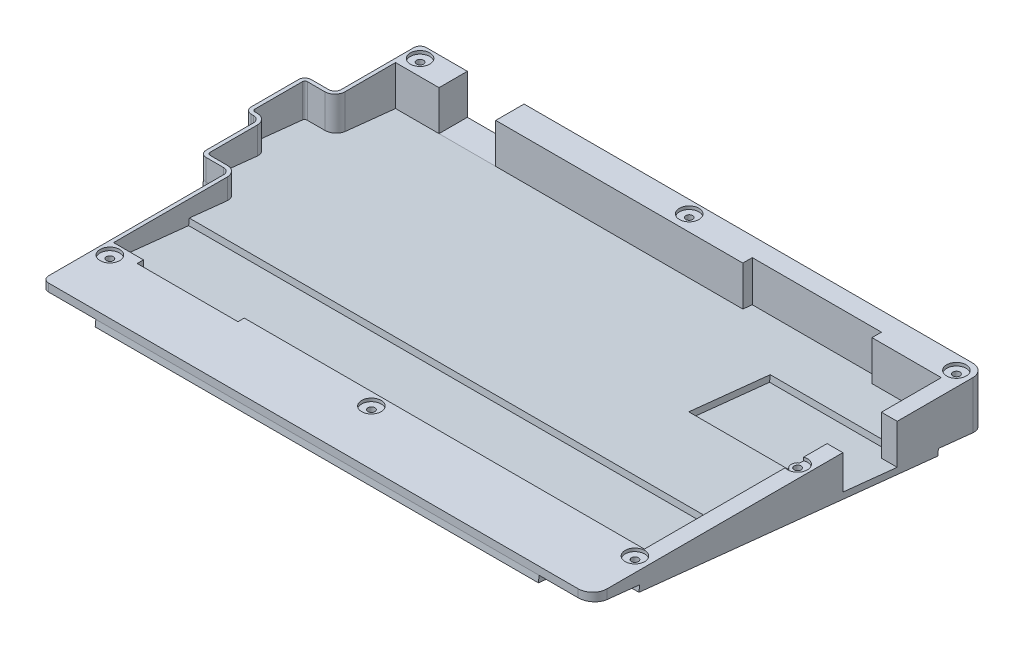
SolidWorks part; units mm, degrees
ref_plane "Front Plane" through (0, 0, 0) normal (0, 0, 1) x (1, 0, 0)
ref_plane "Top Plane" through (0, 0, 0) normal (0, 1, 0) x (1, 0, 0)
ref_plane "Right Plane" through (0, 0, 0) normal (1, 0, 0) x (0, 0, -1)
sketch "Sketch1" plane through (0, 0, 0) normal (0, 1, 0) x (1, 0, 0)
  line L0 (138.4196, 31.7518) -> (125.4196, 31.7518)
  line L1 (-35.0204, 31.7518) -> (107.4196, 31.7518)
  line L2 (140.4196, 29.7518) -> (140.4196, 6.7018)
  line L3 (-34.0204, 3.7518) -> (-34.0204, 22.7518)
  line L4 (136.4596, 27.7518) -> (136.4396, 27.7518)
  line L5 (142.4196, 4.7018) -> (147.9496, 4.7018)
  line L6 (-34.0204, 22.7518) -> (-12.0204, 22.7518)
  line L8 (149.9496, 2.7018) -> (149.9496, -12.3482)
  line L11 (147.9496, -14.3482) -> (147.1896, -14.3482)
  line L14 (145.1896, -16.3482) -> (145.1896, -31.3982)
  line L17 (143.1896, -33.3982) -> (137.6696, -33.3982)
  line L20 (135.6696, -35.3982) -> (135.6696, -77.4982)
  line L21 (-34.0204, -25.6003) -> (-34.0204, -71.4982)
  line L23 (133.6696, -79.4982) -> (-35.0204, -79.4982)
  line L28 (-39.0204, 27.7518) -> (-39.0204, 3.7518)
  line L31 (-34.0204, 3.7518) -> (-39.0204, 3.7518)
  line L32 (-34.0204, -13.4982) -> (-39.0204, -13.4982)
  line L33 (-39.0204, -75.4982) -> (-39.0204, -13.4982)
  line L34 (-34.0204, -71.4982) -> (92.9796, -71.4982)
  line L35 (92.9796, -71.4982) -> (92.9796, -73.4982)
  line L36 (92.9796, -73.4982) -> (124.9796, -73.4982)
  line L37 (124.9796, -73.4982) -> (124.9796, -71.4982)
  line L39 (134.4706, -35.3982) -> (134.4706, -71.4982)
  line L40 (134.4706, -71.4982) -> (124.9796, -71.4982)
  line L41 (137.6696, -32.1992) -> (143.1896, -32.1992)
  line L42 (-34.0204, -13.4982) -> (-34.0204, -22.1362)
  line L43 (143.9906, -31.3982) -> (143.9906, -16.3482)
  line L44 (-12.0204, 22.7518) -> (-12.0204, 25.7518)
  line L45 (147.1896, -13.1492) -> (147.9496, -13.1492)
  line L46 (148.7506, -12.3482) -> (148.7506, 2.7018)
  line L47 (-12.0204, 25.7518) -> (28.9796, 25.7518)
  line L48 (28.9796, 25.7518) -> (28.9796, 22.7518)
  line L49 (28.9796, 22.7518) -> (107.4196, 22.7518)
  line L50 (147.9496, 3.5027) -> (142.4196, 3.5027)
  line L51 (107.4196, 22.7518) -> (107.4196, 31.7518)
  line L52 (139.2206, 6.7018) -> (139.2206, 22.7518)
  line L53 (125.4196, 31.7518) -> (125.4196, 22.7518)
  line L54 (139.2206, 22.7518) -> (125.4196, 22.7518)
  arc A0 (138.4196, 31.7518) -> (140.4196, 29.7518) centre (138.4196, 29.7518) cw
  arc A1 (140.4196, 6.7018) -> (142.4196, 4.7018) centre (142.4196, 6.7018) ccw
  arc A2 (149.9496, 2.7018) -> (147.9496, 4.7018) centre (147.9496, 2.7018) ccw
  arc A3 (149.9496, -12.3482) -> (147.9496, -14.3482) centre (147.9496, -12.3482) cw
  arc A4 (147.1896, -14.3482) -> (145.1896, -16.3482) centre (147.1896, -16.3482) ccw
  arc A5 (145.1896, -31.3982) -> (143.1896, -33.3982) centre (143.1896, -31.3982) cw
  arc A6 (-35.0204, 31.7518) -> (-39.0204, 27.7518) centre (-35.0204, 27.7518) ccw
  arc A7 (-39.0204, -75.4982) -> (-35.0204, -79.4982) centre (-35.0204, -75.4982) ccw
  arc A8 (133.6696, -79.4982) -> (135.6696, -77.4982) centre (133.6696, -77.4982) ccw
  arc A9 (135.6696, -35.3982) -> (137.6696, -33.3982) centre (137.6696, -35.3982) cw
  circle A10 centre (-34.4204, 27.1518) radius 1.1
  circle A11 centre (51.0096, 27.7518) radius 1.1
  circle A12 centre (136.4396, 27.7518) radius 1.1
  circle A13 centre (-34.4204, -74.8982) radius 1.1
  circle A14 centre (48.6296, -75.4982) radius 1.1
  circle A15 centre (131.6496, -75.4982) radius 1.1
  circle A16 centre (-35.0204, -23.8682) radius 1.1
  arc A27 (-34.0204, -22.1362) -> (-34.0204, -25.6003) centre (-35.0204, -23.8682) cw
  arc A28 (139.2206, 6.7018) -> (142.4196, 3.5027) centre (142.4196, 6.7018) ccw
  arc A29 (147.9496, 3.5027) -> (148.7506, 2.7018) centre (147.9496, 2.7018) cw
  arc A30 (148.7506, -12.3482) -> (147.9496, -13.1492) centre (147.9496, -12.3482) cw
  arc A31 (147.1896, -13.1492) -> (143.9906, -16.3482) centre (147.1896, -16.3482) ccw
  arc A32 (143.9906, -31.3982) -> (143.1896, -32.1992) centre (143.1896, -31.3982) cw
  arc A33 (137.6696, -32.1992) -> (134.4706, -35.3982) centre (137.6696, -35.3982) ccw
extrude "Boss-Extrude2" add sketch "Sketch1" against normal blind 4.7 contours L41 A33 L39 L40 L37 L36 L35 L34 L21 A27 L42 L32 L33 A7 L23 A8 L20 A9 L17 A5 L14 A4 L11 A3 L8 A2 L5 A1 L2 A0 L0 L53 L54 L52 A28 L50 A29 L46 A30 L45 A31 L43 A32 A12 A13 A14 A15 | L1 A6 L28 L31 L3 L6 L44 L47 L48 L49 L51 A11 A10 region at (138.2833, 0, -29.6154) region at (31.7683, 0, -26.4895)
move or copy body "Body-Move/Copy1" bodies to move or copy 105 104 copy no rotation origin (55.4646, -2.35, 0) rotation axis (0, 0, 1) rotation angle 180
sketch "Sketch3" plane through (149.9496, 0, 0) normal (1, 0, 0) x (0, 0, -1)
  line L0 (-79.4982, 0) -> (-79.4982, -4.7) construction
  line L1 (-79.4982, 0) -> (-79.4982, -4.7)
  line L2 (31.7518, 0) -> (31.7518, -4.7) construction
  line L3 (31.7518, 0) -> (31.7518, -4.7)
  line L5 (-79.4982, -4.7) -> (31.7518, -16.3928)
  line L6 (31.7518, -16.3928) -> (31.7518, -4.7)
  line L7 (31.7518, -4.7) -> (-79.4982, -4.7)
  line M3 (-75.4982, -4.7) -> (-13.4982, -4.7)
  dimension "D1" = 6
extrude "Boss-Extrude3" add sketch "Sketch3" against normal up to surface (188.97 mm away) contours L6 L7 L5 M3 region at (149.9496, -8.5976, 5.3315) up to face at (-39.0204, -2.35, 4.8232)
sketch "Sketch4" plane through (0, -4.7, 0) normal (0, 1, 0) x (1, 0, 0)
  line L2 (145.9496, -79.4982) -> (149.9496, -79.4982)
  line L3 (149.9496, -79.4982) -> (149.9496, -75.4982)
  line L4 (-29.4904, 6.7018) -> (-29.4904, 29.7518)
  line L5 (-27.4904, 31.7518) -> (-39.0204, 31.7518)
  line L6 (-36.2604, -14.3482) -> (-37.0204, -14.3482)
  line L7 (-39.0204, -12.3482) -> (-39.0204, -79.4982)
  line L8 (-39.0204, -79.4982) -> (-22.7404, -79.4982)
  line L9 (-24.7404, -77.4982) -> (-24.7404, -35.3982)
  line L10 (-26.7404, -33.3982) -> (-32.2604, -33.3982)
  line L11 (-34.2604, -31.3982) -> (-34.2604, -16.3482)
  line L12 (-36.2604, -14.3482) -> (-37.0204, -14.3482)
  line L13 (-39.0204, -12.3482) -> (-39.0204, -79.4982)
  line L14 (-39.0204, -79.4982) -> (-22.7404, -79.4982)
  line L15 (-24.7404, -77.4982) -> (-24.7404, -35.3982)
  line L16 (-26.7404, -33.3982) -> (-32.2604, -33.3982)
  line L17 (-34.2604, -31.3982) -> (-34.2604, -16.3482)
  line L18 (-39.0204, 31.7518) -> (-39.0204, 2.7018)
  line L19 (-37.0204, 4.7018) -> (-31.4904, 4.7018)
  line L20 (-29.4904, 6.7018) -> (-29.4904, 29.7518)
  line L21 (-27.4904, 31.7518) -> (-39.0204, 31.7518)
  line L22 (-39.0204, 31.7518) -> (-39.0204, 2.7018)
  line L23 (-37.0204, 4.7018) -> (-31.4904, 4.7018)
  line L24 (145.9496, -79.4982) -> (149.9496, -79.4982)
  line L25 (149.9496, -79.4982) -> (149.9496, -75.4982)
  line L26 (149.9496, 31.7518) -> (145.9496, 31.7518)
  line L27 (149.9496, 27.7518) -> (149.9496, 31.7518)
  line L28 (149.9496, 31.7518) -> (145.9496, 31.7518)
  line L29 (149.9496, 27.7518) -> (149.9496, 31.7518)
  arc A1 (145.9496, -79.4982) -> (149.9496, -75.4982) centre (145.9496, -75.4982) ccw
  arc A2 (145.9496, -79.4982) -> (149.9496, -75.4982) centre (145.9496, -75.4982) ccw
  arc A3 (-27.4904, 31.7518) -> (-29.4904, 29.7518) centre (-27.4904, 29.7518) ccw
  arc A4 (-37.0204, 4.7018) -> (-39.0204, 2.7018) centre (-37.0204, 2.7018) ccw
  arc A5 (-39.0204, -12.3482) -> (-37.0204, -14.3482) centre (-37.0204, -12.3482) ccw
  arc A6 (-24.7404, -77.4982) -> (-22.7404, -79.4982) centre (-22.7404, -77.4982) ccw
  arc A7 (-24.7404, -35.3982) -> (-26.7404, -33.3982) centre (-26.7404, -35.3982) ccw
  arc A8 (-34.2604, -31.3982) -> (-32.2604, -33.3982) centre (-32.2604, -31.3982) ccw
  arc A9 (-34.2604, -16.3482) -> (-36.2604, -14.3482) centre (-36.2604, -16.3482) ccw
  arc A10 (-39.0204, -12.3482) -> (-37.0204, -14.3482) centre (-37.0204, -12.3482) ccw
  arc A11 (-24.7404, -77.4982) -> (-22.7404, -79.4982) centre (-22.7404, -77.4982) ccw
  arc A12 (-24.7404, -35.3982) -> (-26.7404, -33.3982) centre (-26.7404, -35.3982) ccw
  arc A13 (-34.2604, -31.3982) -> (-32.2604, -33.3982) centre (-32.2604, -31.3982) ccw
  arc A14 (-34.2604, -16.3482) -> (-36.2604, -14.3482) centre (-36.2604, -16.3482) ccw
  arc A15 (-31.4904, 4.7018) -> (-29.4904, 6.7018) centre (-31.4904, 6.7018) ccw
  arc A16 (-27.4904, 31.7518) -> (-29.4904, 29.7518) centre (-27.4904, 29.7518) ccw
  arc A17 (-37.0204, 4.7018) -> (-39.0204, 2.7018) centre (-37.0204, 2.7018) ccw
  arc A18 (-31.4904, 4.7018) -> (-29.4904, 6.7018) centre (-31.4904, 6.7018) ccw
  arc A19 (149.9496, 27.7518) -> (145.9496, 31.7518) centre (145.9496, 27.7518) ccw
  arc A20 (149.9496, 27.7518) -> (145.9496, 31.7518) centre (145.9496, 27.7518) ccw
  dimension "D1" = 0
  dimension "D2" = 0
  dimension "D3" = 0
  dimension "D4" = 0
extrude "Cut-Extrude1" cut sketch "Sketch4" against normal through all
ref_plane "Plane4" through (0, 15, 0) normal (0, 1, 0) x (1, 0, 0)
sketch "Sketch10" plane through (0, 15, 0) normal (0, 1, 0) x (1, 0, 0)
  line L0 (-14.4904, 22.7518) -> (3.5096, 22.7518)
  line L1 (144.9496, 3.7518) -> (144.9496, -13.4982)
  line L27 (-14.4904, 31.7518) -> (-14.4904, 22.7518)
  line L28 (-14.4904, 22.7518) -> (-28.2913, 22.7518)
  line L29 (-28.2913, 22.7518) -> (-28.2913, 6.7018)
  line L30 (-31.4904, 3.5027) -> (-37.0204, 3.5027)
  line L31 (-37.8213, 2.7018) -> (-37.8213, -12.3482)
  line L32 (-37.0204, -13.1492) -> (-36.2604, -13.1492)
  line L33 (-33.0613, -16.3482) -> (-33.0613, -31.3982)
  line L34 (-32.2604, -32.1992) -> (-26.7404, -32.1992)
  line L35 (-23.5413, -35.3982) -> (-23.5413, -71.4982)
  line L36 (-23.5413, -71.4982) -> (-14.0504, -71.4982)
  line L37 (-14.0504, -71.4982) -> (-14.0504, -73.4982)
  line L38 (-14.0504, -73.4982) -> (17.9496, -73.4982)
  line L39 (17.9496, -73.4982) -> (17.9496, -71.4982)
  line L40 (17.9496, -71.4982) -> (144.9496, -71.4982)
  line L41 (144.9496, -71.4982) -> (144.9496, -25.6003)
  line L42 (144.9496, -22.1362) -> (144.9496, -13.4982)
  line L43 (144.9496, -13.4982) -> (149.9496, -13.4982)
  line L44 (149.9496, -13.4982) -> (149.9496, 3.7518)
  line L45 (149.9496, 3.7518) -> (144.9496, 3.7518)
  line L46 (144.9496, 3.7518) -> (144.9496, 22.7518)
  line L47 (144.9496, 22.7518) -> (122.9496, 22.7518)
  line L48 (122.9496, 22.7518) -> (122.9496, 25.7518)
  line L49 (122.9496, 25.7518) -> (81.9496, 25.7518)
  line L50 (81.9496, 25.7518) -> (81.9496, 22.7518)
  line L51 (81.9496, 22.7518) -> (3.5096, 22.7518)
  line L52 (3.5096, 22.7518) -> (3.5096, 31.7518)
  line L53 (3.5096, 31.7518) -> (-14.4904, 31.7518)
  line L54 (-14.4904, 31.7518) -> (-14.4904, 22.7518)
  line L55 (-14.4904, 22.7518) -> (-28.2913, 22.7518)
  line L56 (-28.2913, 22.7518) -> (-28.2913, 6.7018)
  line L57 (-31.4904, 3.5027) -> (-37.0204, 3.5027)
  line L58 (-37.8213, 2.7018) -> (-37.8213, -12.3482)
  line L59 (-37.0204, -13.1492) -> (-36.2604, -13.1492)
  line L60 (-33.0613, -16.3482) -> (-33.0613, -31.3982)
  line L61 (-32.2604, -32.1992) -> (-26.7404, -32.1992)
  line L62 (-23.5413, -35.3982) -> (-23.5413, -71.4982)
  line L63 (-23.5413, -71.4982) -> (-14.0504, -71.4982)
  line L64 (-14.0504, -71.4982) -> (-14.0504, -73.4982)
  line L65 (-14.0504, -73.4982) -> (17.9496, -73.4982)
  line L66 (17.9496, -73.4982) -> (17.9496, -71.4982)
  line L67 (17.9496, -71.4982) -> (144.9496, -71.4982)
  line L68 (144.9496, -71.4982) -> (144.9496, -25.6003)
  line L69 (144.9496, -22.1362) -> (144.9496, -13.4982)
  line L70 (144.9496, -13.4982) -> (149.9496, -13.4982)
  line L71 (149.9496, -13.4982) -> (149.9496, 3.7518)
  line L72 (149.9496, 3.7518) -> (144.9496, 3.7518)
  line L73 (144.9496, 3.7518) -> (144.9496, 22.7518)
  line L74 (144.9496, 22.7518) -> (122.9496, 22.7518)
  line L75 (122.9496, 22.7518) -> (122.9496, 25.7518)
  line L76 (122.9496, 25.7518) -> (81.9496, 25.7518)
  line L77 (81.9496, 25.7518) -> (81.9496, 22.7518)
  line L78 (81.9496, 22.7518) -> (3.5096, 22.7518)
  line L79 (3.5096, 22.7518) -> (3.5096, 31.7518)
  line L80 (3.5096, 31.7518) -> (-14.4904, 31.7518)
  arc A7 (-31.4904, 3.5027) -> (-28.2913, 6.7018) centre (-31.4904, 6.7018) ccw
  arc A8 (-37.0204, 3.5027) -> (-37.8213, 2.7018) centre (-37.0204, 2.7018) ccw
  arc A9 (-37.8213, -12.3482) -> (-37.0204, -13.1492) centre (-37.0204, -12.3482) ccw
  arc A10 (-33.0613, -16.3482) -> (-36.2604, -13.1492) centre (-36.2604, -16.3482) ccw
  arc A11 (-33.0613, -31.3982) -> (-32.2604, -32.1992) centre (-32.2604, -31.3982) ccw
  arc A12 (-23.5413, -35.3982) -> (-26.7404, -32.1992) centre (-26.7404, -35.3982) ccw
  arc A13 (144.9496, -22.1362) -> (144.9496, -25.6003) centre (145.9496, -23.8682) ccw
  arc A14 (-31.4904, 3.5027) -> (-28.2913, 6.7018) centre (-31.4904, 6.7018) ccw
  arc A15 (-37.0204, 3.5027) -> (-37.8213, 2.7018) centre (-37.0204, 2.7018) ccw
  arc A16 (-37.8213, -12.3482) -> (-37.0204, -13.1492) centre (-37.0204, -12.3482) ccw
  arc A17 (-33.0613, -16.3482) -> (-36.2604, -13.1492) centre (-36.2604, -16.3482) ccw
  arc A18 (-33.0613, -31.3982) -> (-32.2604, -32.1992) centre (-32.2604, -31.3982) ccw
  arc A19 (-23.5413, -35.3982) -> (-26.7404, -32.1992) centre (-26.7404, -35.3982) ccw
  arc A20 (144.9496, -22.1362) -> (144.9496, -25.6003) centre (145.9496, -23.8682) ccw
  dimension "D1" = 0
extrude "Cut-Extrude2" cut sketch "Sketch10" against normal through all contours A20 L69 L1 L73 L74 L75 L76 L77 L78 L0 L55 L56 A14 L57 A15 L58 A16 L59 A17 L60 A18 L61 A19 L62 L63 L64 L65 L66 L67 L68 region at (57.9798, 15, 23.6888)
sketch "Sketch11" plane through (144.9496, 0, 0) normal (-1, 0, 0) x (0, 0, 1)
  line L0 (-22.7518, -15.4469) -> (71.4982, -5.5408)
  line L1 (71.4982, -5.5408) -> (71.4982, -3.5408)
  line L2 (71.4982, 0) -> (71.4982, -5.5408) construction
  line L3 (71.4982, -3.5408) -> (-22.7518, -13.4469)
  line L4 (-22.7518, 0) -> (-22.7518, -15.4469) construction
  line L5 (-22.7518, -13.4469) -> (-22.7518, -15.4469)
  dimension "D1" = 2
  dimension "D2" = 2
extrude "Boss-Extrude4" add sketch "Sketch11" along normal up to surface (182.7709 mm away)
sketch "Sketch12" plane through (0, -10.9348, 1.1493) normal (0, 0.9945, -0.1045) x (1, 0, 0)
  line L0 (-29.4904, 7.8943) -> (-29.4904, 24.0327) construction
  line L1 (-29.4904, 24.0327) -> (-37.8213, 24.0327) construction
  line L2 (-37.8213, 24.0327) -> (-37.8213, 5.715) construction
  line L3 (-37.0204, 5.8833) -> (-31.4904, 5.8833) construction
  line L4 (-36.2604, -13.2716) -> (-37.0204, -13.2716) construction
  line L5 (-37.8213, -13.1033) -> (-37.8213, -70.7364) construction
  line L6 (-37.8213, -70.7364) -> (-24.7404, -70.7364) construction
  line L7 (-24.7404, -70.7364) -> (-24.7404, -34.4376) construction
  line L8 (-26.7404, -32.4266) -> (-32.2604, -32.4266) construction
  line L9 (-34.2604, -30.4155) -> (-34.2604, -15.2826) construction
  line L10 (-29.4904, 7.8943) -> (-29.4904, 24.0327)
  line L11 (-29.4904, 24.0327) -> (-37.8213, 24.0327)
  line L12 (-37.8213, 24.0327) -> (-37.8213, 5.715)
  line L13 (-37.0204, 5.8833) -> (-31.4904, 5.8833)
  line L14 (-36.2604, -13.2716) -> (-37.0204, -13.2716)
  line L15 (-37.8213, -13.1033) -> (-37.8213, -70.7364)
  line L16 (-37.8213, -70.7364) -> (-24.7404, -70.7364)
  line L17 (-24.7404, -70.7364) -> (-24.7404, -34.4376)
  line L18 (-26.7404, -32.4266) -> (-32.2604, -32.4266)
  line L19 (-34.2604, -30.4155) -> (-34.2604, -15.2826)
  line L20 (-37.8213, 24.0327) -> (-37.8213, 25.9101)
  line L21 (-29.4904, 24.0327) -> (-29.4904, 27.1127)
  line L22 (-29.4904, 27.1127) -> (-37.8213, 25.9101)
  ellipse E0 centre (-31.4904, 7.8943) end of major axis (-31.4904, 9.9053) minor radius 2 (-31.4904, 5.8833) -> (-29.4904, 7.8943) ccw construction
  ellipse E1 centre (-37.0204, 3.8723) end of major axis (-37.0204, 5.8833) minor radius 2 (-37.0204, 5.8833) -> (-37.8213, 5.715) ccw construction
  ellipse E2 centre (-37.0204, -11.2606) end of major axis (-37.0204, -9.2496) minor radius 2 (-37.8213, -13.1033) -> (-37.0204, -13.2716) ccw construction
  ellipse E3 centre (-26.7404, -34.4376) end of major axis (-26.7404, -32.4266) minor radius 2 (-24.7404, -34.4376) -> (-26.7404, -32.4266) ccw construction
  ellipse E4 centre (-32.2604, -30.4155) end of major axis (-32.2604, -28.4045) minor radius 2 (-34.2604, -30.4155) -> (-32.2604, -32.4266) ccw construction
  ellipse E5 centre (-36.2604, -15.2826) end of major axis (-36.2604, -13.2716) minor radius 2 (-34.2604, -15.2826) -> (-36.2604, -13.2716) ccw construction
  ellipse E6 centre (-31.4904, 7.8943) end of major axis (-31.4904, 9.9053) minor radius 2 (-31.4904, 5.8833) -> (-29.4904, 7.8943) ccw
  ellipse E7 centre (-37.0204, 3.8723) end of major axis (-37.0204, 5.8833) minor radius 2 (-37.0204, 5.8833) -> (-37.8213, 5.715) ccw
  ellipse E8 centre (-37.0204, -11.2606) end of major axis (-37.0204, -9.2496) minor radius 2 (-37.8213, -13.1033) -> (-37.0204, -13.2716) ccw
  ellipse E9 centre (-26.7404, -34.4376) end of major axis (-26.7404, -32.4266) minor radius 2 (-24.7404, -34.4376) -> (-26.7404, -32.4266) ccw
  ellipse E10 centre (-32.2604, -30.4155) end of major axis (-32.2604, -28.4045) minor radius 2 (-34.2604, -30.4155) -> (-32.2604, -32.4266) ccw
  ellipse E11 centre (-36.2604, -15.2826) end of major axis (-36.2604, -13.2716) minor radius 2 (-34.2604, -15.2826) -> (-36.2604, -13.2716) ccw
sketch "Sketch26" plane through (-37.8213, 0, 0) normal (-1, 0, 0) x (0, 0, 1)
  line L0 (14.1808, -9.5651) -> (-4.5344, -11.5322)
  line L1 (-4.5344, -13.5322) -> (14.1808, -11.5651)
  line L4 (-22.7518, -15.4469) -> (-4.5344, -13.5322)
  line L5 (-4.5344, -13.5322) -> (-4.5344, -11.5322)
  line L6 (-4.5344, -11.5322) -> (-22.7518, -13.4469)
  line L7 (-22.7518, -13.4469) -> (-22.7518, -15.4469)
  line L8 (-22.7518, -15.4469) -> (-4.5344, -13.5322)
  line L9 (-4.5344, -13.5322) -> (-4.5344, -11.5322)
  line L10 (-4.5344, -11.5322) -> (-22.7518, -13.4469)
  line L11 (-22.7518, -13.4469) -> (-22.7518, -15.4469)
  line L12 (14.1808, -9.5651) -> (14.1808, -11.5651)
  line L13 (14.1808, -11.5651) -> (71.4982, -5.5408)
  line L14 (71.4982, -5.5408) -> (71.4982, -3.5408)
  line L15 (71.4982, -3.5408) -> (14.1808, -9.5651)
  line L16 (14.1808, -9.5651) -> (14.1808, -11.5651)
  line L17 (14.1808, -11.5651) -> (71.4982, -5.5408)
  line L18 (71.4982, -5.5408) -> (71.4982, -3.5408)
  line L19 (71.4982, -3.5408) -> (14.1808, -9.5651)
  line M9 (14.1808, -9.5651) -> (14.1808, -11.5651)
  line M10 (14.1808, -11.5651) -> (71.4982, -5.5408)
  line M11 (71.4982, -5.5408) -> (71.4982, -3.5408)
  line M12 (71.4982, -3.5408) -> (14.1808, -9.5651)
  dimension "D1" = 0
  dimension "D2" = 0
extrude "Boss-Extrude10" add sketch "Sketch26" along normal blind 11 contours L10 L11 L8 L9 | L9 L1 L0 M9 | M12 M9 M10 M11 region at (-37.8213, -11.5487, 4.8232) region at (-37.8213, -7.553, 42.8395) region at (-37.8213, -13.4895, -13.6431)
sketch "Sketch28" plane through (0, -10.9348, 1.1493) normal (0, 0.9945, -0.1045) x (1, 0, 0)
  line L0 (-48.8213, 24.0327) -> (-52.7132, 28.3929)
  line L1 (-52.7132, 28.3929) -> (-29.4904, 30.8021)
  line L2 (-29.4904, 30.8021) -> (-29.4904, 24.0327)
  line L10 (-29.4904, 7.8943) -> (-29.4904, 24.0327)
  line L11 (-29.4904, 24.0327) -> (-48.8213, 24.0327)
  line L12 (-48.8213, 24.0327) -> (-48.8213, -70.7364)
  line L13 (-48.8213, -70.7364) -> (-24.7404, -70.7364)
  line L14 (-24.7404, -70.7364) -> (-24.7404, -34.4376)
  line L15 (-26.7404, -32.4266) -> (-32.2604, -32.4266)
  line L16 (-34.2604, -30.4155) -> (-34.2604, -15.2826)
  line L17 (-36.2604, -13.2716) -> (-37.0204, -13.2716)
  line L18 (-39.0204, -11.2606) -> (-39.0204, 3.8723)
  line L19 (-37.0204, 5.8833) -> (-31.4904, 5.8833)
  line L20 (-29.4904, 7.8943) -> (-29.4904, 24.0327)
  line L21 (-29.4904, 24.0327) -> (-48.8213, 24.0327)
  line L22 (-48.8213, 24.0327) -> (-48.8213, -70.7364)
  line L23 (-48.8213, -70.7364) -> (-24.7404, -70.7364)
  line L24 (-24.7404, -70.7364) -> (-24.7404, -34.4376)
  line L25 (-26.7404, -32.4266) -> (-32.2604, -32.4266)
  line L26 (-34.2604, -30.4155) -> (-34.2604, -15.2826)
  line L27 (-36.2604, -13.2716) -> (-37.0204, -13.2716)
  line L28 (-39.0204, -11.2606) -> (-39.0204, 3.8723)
  line L29 (-37.0204, 5.8833) -> (-31.4904, 5.8833)
  ellipse E6 centre (-31.4904, 7.8943) end of major axis (-31.4904, 9.9053) minor radius 2 (-31.4904, 5.8833) -> (-29.4904, 7.8943) ccw
  ellipse E7 centre (-26.7404, -34.4376) end of major axis (-26.7404, -32.4266) minor radius 2 (-24.7404, -34.4376) -> (-26.7404, -32.4266) ccw
  ellipse E8 centre (-32.2604, -30.4155) end of major axis (-32.2604, -28.4045) minor radius 2 (-34.2604, -30.4155) -> (-32.2604, -32.4266) ccw
  ellipse E9 centre (-36.2604, -15.2826) end of major axis (-36.2604, -13.2716) minor radius 2 (-34.2604, -15.2826) -> (-36.2604, -13.2716) ccw
  ellipse E10 centre (-37.0204, -11.2606) end of major axis (-37.0204, -9.2496) minor radius 2 (-39.0204, -11.2606) -> (-37.0204, -13.2716) ccw
  ellipse E11 centre (-37.0204, 3.8723) end of major axis (-37.0204, 5.8833) minor radius 2 (-37.0204, 5.8833) -> (-39.0204, 3.8723) ccw
  ellipse E12 centre (-31.4904, 7.8943) end of major axis (-31.4904, 9.9053) minor radius 2 (-31.4904, 5.8833) -> (-29.4904, 7.8943) ccw
  ellipse E13 centre (-26.7404, -34.4376) end of major axis (-26.7404, -32.4266) minor radius 2 (-24.7404, -34.4376) -> (-26.7404, -32.4266) ccw
  ellipse E14 centre (-32.2604, -30.4155) end of major axis (-32.2604, -28.4045) minor radius 2 (-34.2604, -30.4155) -> (-32.2604, -32.4266) ccw
  ellipse E15 centre (-36.2604, -15.2826) end of major axis (-36.2604, -13.2716) minor radius 2 (-34.2604, -15.2826) -> (-36.2604, -13.2716) ccw
  ellipse E16 centre (-37.0204, -11.2606) end of major axis (-37.0204, -9.2496) minor radius 2 (-39.0204, -11.2606) -> (-37.0204, -13.2716) ccw
  ellipse E17 centre (-37.0204, 3.8723) end of major axis (-37.0204, 5.8833) minor radius 2 (-37.0204, 5.8833) -> (-39.0204, 3.8723) ccw
  ellipse M17 centre (-31.4904, 7.8943) end of major axis (-31.4904, 9.9053) minor radius 2 (-31.4904, 5.8833) -> (-29.4904, 7.8943) ccw
  line M18 (-29.4904, 7.8943) -> (-29.4904, 24.0327)
  line M19 (-29.4904, 24.0327) -> (-48.8213, 24.0327)
  line M20 (-48.8213, 24.0327) -> (-48.8213, -70.7364)
  line M21 (-48.8213, -70.7364) -> (-24.7404, -70.7364)
  line M22 (-24.7404, -70.7364) -> (-24.7404, -34.4376)
  ellipse M23 centre (-26.7404, -34.4376) end of major axis (-26.7404, -32.4266) minor radius 2 (-24.7404, -34.4376) -> (-26.7404, -32.4266) ccw
  line M24 (-26.7404, -32.4266) -> (-32.2604, -32.4266)
  ellipse M25 centre (-32.2604, -30.4155) end of major axis (-32.2604, -28.4045) minor radius 2 (-32.2604, -32.4266) -> (-34.2604, -30.4155) cw
  line M26 (-34.2604, -30.4155) -> (-34.2604, -15.2826)
  ellipse M27 centre (-36.2604, -15.2826) end of major axis (-36.2604, -13.2716) minor radius 2 (-34.2604, -15.2826) -> (-36.2604, -13.2716) ccw
  line M28 (-36.2604, -13.2716) -> (-37.0204, -13.2716)
  ellipse M29 centre (-37.0204, -11.2606) end of major axis (-37.0204, -9.2496) minor radius 2 (-37.0204, -13.2716) -> (-39.0204, -11.2606) cw
  line M30 (-39.0204, -11.2606) -> (-39.0204, 3.8723)
  ellipse M31 centre (-37.0204, 3.8723) end of major axis (-37.0204, 5.8833) minor radius 2 (-39.0204, 3.8723) -> (-37.0204, 5.8833) cw
  line M32 (-37.0204, 5.8833) -> (-31.4904, 5.8833)
  dimension "D1" = 0
extrude "Cut-Extrude8" cut sketch "Sketch28" against normal blind 11 contours M32 M17 M18 M19 M20 M21 M22 M23 M24 M25 M26 M27 M28 M29 M30 M31 | L2 L1 L0 M19 region at (-39.4803, -13.7524, -25.6581) region at (-38.8035, -7.967, 29.3861)
sketch "Sketch30" plane through (122.9496, 0, 0) normal (-1, 0, 0) x (0, 0, 1)
  line L0 (-25.7518, -15.7622) -> (-22.7518, -15.4469)
  line L1 (-22.7518, -15.4469) -> (-22.7518, -13.4469)
  line L2 (-22.7518, -15.4469) -> (-22.7518, -13.4469) construction
  line L3 (-22.7518, -13.4469) -> (-25.7518, -13.7622)
  line L4 (-25.7518, 0) -> (-25.7518, -15.7622) construction
  line L5 (-25.7518, -13.7622) -> (-25.7518, -15.7622)
extrude "Boss-Extrude11" add sketch "Sketch30" along normal up to surface (41 mm away)
sketch "Sketch32" plane through (17.9496, 0, 0) normal (-1, 0, 0) x (0, 0, 1)
  line L0 (73.4982, -5.3306) -> (71.4982, -5.5408)
  line L1 (71.4982, -5.5408) -> (71.4982, -3.5408)
  line L2 (71.4982, -3.5408) -> (73.4982, -3.3306)
  line L3 (73.4982, 0) -> (73.4982, -5.3306) construction
  line L4 (73.4982, -3.3306) -> (73.4982, -5.3306)
  dimension "D1" = 2
extrude "Boss-Extrude14" add sketch "Sketch32" along normal up to surface (32 mm away)
sketch "Sketch35" plane through (0, 0, 0) normal (0, 1, 0) x (1, 0, 0)
  line L0 (149.9496, 3.7518) -> (149.9496, -13.4982)
  line L1 (149.9496, -13.4982) -> (144.9496, -13.4982)
  line L2 (144.9496, -13.4982) -> (144.9496, 3.7518)
  line L3 (144.9496, 3.7518) -> (149.9496, 3.7518)
ref_plane "Plane5" through (149.9496, -5.1204, 75.4982) normal (0, -1, 0) x (-1, 0, 0)
sketch "Sketch47" plane through (0, 0, 0) normal (0, 1, 0) x (1, 0, 0)
  circle A0 centre (145.3496, -74.8982) radius 3.1
  circle A1 centre (62.2996, -75.4982) radius 3.1
  circle A2 centre (-20.7204, -75.4982) radius 3.1
  circle A3 centre (-25.5104, 27.7518) radius 3.1
  circle A4 centre (59.9196, 27.7518) radius 3.1
  circle A5 centre (145.3496, 27.1518) radius 3.1
  circle A6 centre (145.9496, -23.8682) radius 3.1
extrude "Cut-Extrude17" cut sketch "Sketch47" against normal blind 1.8
sketch "Sketch48" plane through (0, 0, 0) normal (0, 1, 0) x (1, 0, 0)
  line L10 (145.9496, 31.7518) -> (3.5096, 31.7518)
  line L11 (3.5096, 31.7518) -> (3.5096, 22.7518)
  line L12 (3.5096, 22.7518) -> (81.9496, 22.7518)
  line L13 (81.9496, 22.7518) -> (81.9496, 25.7518)
  line L14 (81.9496, 25.7518) -> (122.9496, 25.7518)
  line L15 (122.9496, 25.7518) -> (122.9496, 22.7518)
  line L16 (122.9496, 22.7518) -> (144.9496, 22.7518)
  line L17 (144.9496, 22.7518) -> (144.9496, 3.7518)
  line L18 (144.9496, 3.7518) -> (149.9496, 3.7518)
  line L19 (149.9496, 3.7518) -> (149.9496, 27.7518)
  line L20 (145.9496, 31.7518) -> (3.5096, 31.7518)
  line L21 (3.5096, 31.7518) -> (3.5096, 22.7518)
  line L22 (3.5096, 22.7518) -> (81.9496, 22.7518)
  line L23 (81.9496, 22.7518) -> (81.9496, 25.7518)
  line L24 (81.9496, 25.7518) -> (122.9496, 25.7518)
  line L25 (122.9496, 25.7518) -> (122.9496, 22.7518)
  line L26 (122.9496, 22.7518) -> (144.9496, 22.7518)
  line L27 (144.9496, 22.7518) -> (144.9496, 3.7518)
  line L28 (144.9496, 3.7518) -> (149.9496, 3.7518)
  line L29 (149.9496, 3.7518) -> (149.9496, 27.7518)
  line L47 (144.9496, -13.4982) -> (144.9496, -20.9339)
  line L48 (144.9496, -26.8025) -> (144.9496, -71.4982)
  line L49 (144.9496, -71.4982) -> (17.9496, -71.4982)
  line L50 (17.9496, -71.4982) -> (17.9496, -73.4982)
  line L51 (17.9496, -73.4982) -> (-14.0504, -73.4982)
  line L52 (-14.0504, -73.4982) -> (-14.0504, -71.4982)
  line L53 (-14.0504, -71.4982) -> (-23.5413, -71.4982)
  line L54 (-23.5413, -71.4982) -> (-23.5413, -35.3982)
  line L55 (-26.7404, -32.1992) -> (-32.2604, -32.1992)
  line L56 (-33.0613, -31.3982) -> (-33.0613, -16.3482)
  line L57 (-36.2604, -13.1492) -> (-37.0204, -13.1492)
  line L58 (-37.8213, -12.3482) -> (-37.8213, 2.7018)
  line L59 (-37.0204, 3.5027) -> (-31.4904, 3.5027)
  line L60 (-28.2913, 6.7018) -> (-28.2913, 22.7518)
  line L61 (-28.2913, 22.7518) -> (-14.4904, 22.7518)
  line L62 (-14.4904, 22.7518) -> (-14.4904, 31.7518)
  line L63 (-14.4904, 31.7518) -> (-27.4904, 31.7518)
  line L64 (-29.4904, 29.7518) -> (-29.4904, 6.7018)
  line L65 (-31.4904, 4.7018) -> (-37.0204, 4.7018)
  line L66 (-39.0204, 2.7018) -> (-39.0204, -12.3482)
  line L67 (-37.0204, -14.3482) -> (-36.2604, -14.3482)
  line L68 (-34.2604, -16.3482) -> (-34.2604, -31.3982)
  line L69 (-32.2604, -33.3982) -> (-26.7404, -33.3982)
  line L70 (-24.7404, -35.3982) -> (-24.7404, -77.4982)
  line L71 (-22.7404, -79.4982) -> (145.9496, -79.4982)
  line L72 (149.9496, -75.4982) -> (149.9496, -13.4982)
  line L73 (149.9496, -13.4982) -> (144.9496, -13.4982)
  line L74 (144.9496, -13.4982) -> (144.9496, -20.9339)
  line L75 (144.9496, -26.8025) -> (144.9496, -71.4982)
  line L76 (144.9496, -71.4982) -> (17.9496, -71.4982)
  line L77 (17.9496, -71.4982) -> (17.9496, -73.4982)
  line L78 (17.9496, -73.4982) -> (-14.0504, -73.4982)
  line L79 (-14.0504, -73.4982) -> (-14.0504, -71.4982)
  line L80 (-14.0504, -71.4982) -> (-23.5413, -71.4982)
  line L81 (-23.5413, -71.4982) -> (-23.5413, -35.3982)
  line L82 (-26.7404, -32.1992) -> (-32.2604, -32.1992)
  line L83 (-33.0613, -31.3982) -> (-33.0613, -16.3482)
  line L84 (-36.2604, -13.1492) -> (-37.0204, -13.1492)
  line L85 (-37.8213, -12.3482) -> (-37.8213, 2.7018)
  line L86 (-37.0204, 3.5027) -> (-31.4904, 3.5027)
  line L87 (-28.2913, 6.7018) -> (-28.2913, 22.7518)
  line L88 (-28.2913, 22.7518) -> (-14.4904, 22.7518)
  line L89 (-14.4904, 22.7518) -> (-14.4904, 31.7518)
  line L90 (-14.4904, 31.7518) -> (-27.4904, 31.7518)
  line L91 (-29.4904, 29.7518) -> (-29.4904, 6.7018)
  line L92 (-31.4904, 4.7018) -> (-37.0204, 4.7018)
  line L93 (-39.0204, 2.7018) -> (-39.0204, -12.3482)
  line L94 (-37.0204, -14.3482) -> (-36.2604, -14.3482)
  line L95 (-34.2604, -16.3482) -> (-34.2604, -31.3982)
  line L96 (-32.2604, -33.3982) -> (-26.7404, -33.3982)
  line L97 (-24.7404, -35.3982) -> (-24.7404, -77.4982)
  line L98 (-22.7404, -79.4982) -> (145.9496, -79.4982)
  line L99 (149.9496, -75.4982) -> (149.9496, -13.4982)
  line L100 (149.9496, -13.4982) -> (144.9496, -13.4982)
  arc A1 (149.9496, 27.7518) -> (145.9496, 31.7518) centre (145.9496, 27.7518) ccw
  arc A2 (149.9496, 27.7518) -> (145.9496, 31.7518) centre (145.9496, 27.7518) ccw
  arc A18 (144.9496, -26.8025) -> (144.9496, -20.9339) centre (145.9496, -23.8682) ccw
  arc A19 (-23.5413, -35.3982) -> (-26.7404, -32.1992) centre (-26.7404, -35.3982) ccw
  arc A20 (-33.0613, -31.3982) -> (-32.2604, -32.1992) centre (-32.2604, -31.3982) ccw
  arc A21 (-33.0613, -16.3482) -> (-36.2604, -13.1492) centre (-36.2604, -16.3482) ccw
  arc A22 (-37.8213, -12.3482) -> (-37.0204, -13.1492) centre (-37.0204, -12.3482) ccw
  arc A23 (-37.0204, 3.5027) -> (-37.8213, 2.7018) centre (-37.0204, 2.7018) ccw
  arc A24 (-31.4904, 3.5027) -> (-28.2913, 6.7018) centre (-31.4904, 6.7018) ccw
  arc A25 (-27.4904, 31.7518) -> (-29.4904, 29.7518) centre (-27.4904, 29.7518) ccw
  arc A26 (-31.4904, 4.7018) -> (-29.4904, 6.7018) centre (-31.4904, 6.7018) ccw
  arc A27 (-37.0204, 4.7018) -> (-39.0204, 2.7018) centre (-37.0204, 2.7018) ccw
  arc A28 (-39.0204, -12.3482) -> (-37.0204, -14.3482) centre (-37.0204, -12.3482) ccw
  arc A29 (-34.2604, -16.3482) -> (-36.2604, -14.3482) centre (-36.2604, -16.3482) ccw
  arc A30 (-34.2604, -31.3982) -> (-32.2604, -33.3982) centre (-32.2604, -31.3982) ccw
  arc A31 (-24.7404, -35.3982) -> (-26.7404, -33.3982) centre (-26.7404, -35.3982) ccw
  arc A32 (-24.7404, -77.4982) -> (-22.7404, -79.4982) centre (-22.7404, -77.4982) ccw
  arc A33 (145.9496, -79.4982) -> (149.9496, -75.4982) centre (145.9496, -75.4982) ccw
  arc A34 (144.9496, -26.8025) -> (144.9496, -20.9339) centre (145.9496, -23.8682) ccw
  arc A35 (-23.5413, -35.3982) -> (-26.7404, -32.1992) centre (-26.7404, -35.3982) ccw
  arc A36 (-33.0613, -31.3982) -> (-32.2604, -32.1992) centre (-32.2604, -31.3982) ccw
  arc A37 (-33.0613, -16.3482) -> (-36.2604, -13.1492) centre (-36.2604, -16.3482) ccw
  arc A38 (-37.8213, -12.3482) -> (-37.0204, -13.1492) centre (-37.0204, -12.3482) ccw
  arc A39 (-37.0204, 3.5027) -> (-37.8213, 2.7018) centre (-37.0204, 2.7018) ccw
  arc A40 (-31.4904, 3.5027) -> (-28.2913, 6.7018) centre (-31.4904, 6.7018) ccw
  arc A41 (-27.4904, 31.7518) -> (-29.4904, 29.7518) centre (-27.4904, 29.7518) ccw
  arc A42 (-31.4904, 4.7018) -> (-29.4904, 6.7018) centre (-31.4904, 6.7018) ccw
  arc A43 (-37.0204, 4.7018) -> (-39.0204, 2.7018) centre (-37.0204, 2.7018) ccw
  arc A44 (-39.0204, -12.3482) -> (-37.0204, -14.3482) centre (-37.0204, -12.3482) ccw
  arc A45 (-34.2604, -16.3482) -> (-36.2604, -14.3482) centre (-36.2604, -16.3482) ccw
  arc A46 (-34.2604, -31.3982) -> (-32.2604, -33.3982) centre (-32.2604, -31.3982) ccw
  arc A47 (-24.7404, -35.3982) -> (-26.7404, -33.3982) centre (-26.7404, -35.3982) ccw
  arc A48 (-24.7404, -77.4982) -> (-22.7404, -79.4982) centre (-22.7404, -77.4982) ccw
  arc A49 (145.9496, -79.4982) -> (149.9496, -75.4982) centre (145.9496, -75.4982) ccw
  dimension "D1" = 0
  dimension "D2" = 0
extrude "Cut-Extrude18" cut sketch "Sketch48" against normal blind 0.8
sketch "Sketch49" plane through (0, -12.913, 1.3572) normal (0, -0.9945, 0.1045) x (1, 0, 0)
  line L0 (17.9496, 70.7364) -> (144.9496, 70.7364) construction
  line L1 (17.9496, 70.7364) -> (144.9496, 70.7364)
  line L2 (-23.5413, 46.5714) -> (-23.5413, 70.7364)
  line L6 (144.9496, 46.5714) -> (144.9496, 70.7364)
  line L9 (17.9496, 70.7364) -> (-23.5413, 70.7364)
  line L10 (144.9496, 46.5714) -> (-23.5413, 46.5714)
extrude "Cut-Extrude19" cut sketch "Sketch49" against normal blind 10
sketch "Sketch50" plane through (0, -12.913, 1.3572) normal (0, -0.9945, 0.1045) x (1, 0, 0)
  line L5 (105.9496, 17.3552) -> (105.9496, -8.6448)
  line L7 (144.9496, -8.6448) -> (144.9496, 17.3552)
  line L12 (105.9496, -8.6448) -> (144.9496, -8.6448)
  line L13 (105.9496, 17.3552) -> (144.9496, 17.3552)
extrude "Cut-Extrude20" cut sketch "Sketch50" against normal blind 10
sketch "Sketch51" plane through (0, 0, 79.4982) normal (0, 0, 1) x (1, 0, 0)
  line L4 (145.9496, -0.8) -> (-22.7404, -0.8)
  line L5 (-22.7404, -0.8) -> (-22.7404, -4.7)
  line L6 (-22.7404, -4.7) -> (145.9496, -4.7)
  line L7 (145.9496, -4.7) -> (145.9496, -0.8)
  line L8 (145.9496, -0.8) -> (-22.7404, -0.8)
  line L9 (-22.7404, -0.8) -> (-22.7404, -4.7)
  line L10 (-22.7404, -4.7) -> (145.9496, -4.7)
  line L11 (145.9496, -4.7) -> (145.9496, -0.8)
  dimension "D1" = 0
extrude "Boss-Extrude15" add sketch "Sketch51" along normal blind 13.5
sketch "Sketch52" plane through (0, 0, 92.9982) normal (0, 0, 1) x (1, 0, 0)
  line L4 (145.9496, -4.7) -> (145.9496, -0.8)
  line L5 (145.9496, -0.8) -> (-22.7404, -0.8)
  line L6 (-22.7404, -0.8) -> (-22.7404, -4.7)
  line L7 (-22.7404, -4.7) -> (145.9496, -4.7)
  line L8 (145.9496, -4.7) -> (145.9496, -0.8)
  line L9 (145.9496, -0.8) -> (-22.7404, -0.8)
  line L10 (-22.7404, -0.8) -> (-22.7404, -4.7)
  line L11 (-22.7404, -4.7) -> (145.9496, -4.7)
  dimension "D1" = 0
extrude "Cut-Extrude21" cut sketch "Sketch52" against normal blind 13.5
sketch "Sketch53" plane through (149.9496, 0, 0) normal (1, 0, 0) x (0, 0, -1)
  line L0 (-79.4982, -4.7) -> (-92.9243, -3.2889)
  line L1 (-79.4982, -0.8) -> (-92.9243, -0.8)
  line L2 (-92.9243, -0.8) -> (-92.9243, -3.2889)
  line L4 (-75.4982, -5.1204) -> (-75.4982, -0.8)
  line L5 (-75.4982, -0.8) -> (-79.4982, -0.8)
  line L6 (-79.4982, -0.8) -> (-79.4982, -4.7)
  line L7 (-79.4982, -4.7) -> (-75.4982, -5.1204)
  line L8 (-75.4982, -5.1204) -> (-75.4982, -0.8)
  line L9 (-75.4982, -0.8) -> (-79.4982, -0.8)
  line L10 (-79.4982, -0.8) -> (-79.4982, -4.7)
  line L11 (-79.4982, -4.7) -> (-75.4982, -5.1204)
  dimension "D1" = 0
extrude "Boss-Extrude16" add sketch "Sketch53" against normal up to surface (174.69 mm away) contours L10 L1 L2 L0 region at (149.9496, -2.4232, 85.717)
sketch "Sketch54" plane through (0, 0, 79.4982) normal (0, 0, -1) x (-1, 0, 0)
  line L0 (22.7404, -4.7) -> (22.7404, -6.6661)
  line L1 (22.7404, -6.6661) -> (24.7404, -6.6661)
  line L2 (24.7404, -6.6661) -> (24.7404, -4.7)
  line L4 (22.7404, -0.8) -> (22.7404, -4.7)
  line L5 (22.7404, -4.7) -> (24.7404, -4.7)
  line L6 (24.7404, -4.7) -> (24.7404, -0.8)
  line L7 (24.7404, -0.8) -> (22.7404, -0.8)
  line L8 (22.7404, -0.8) -> (22.7404, -4.7)
  line L9 (22.7404, -4.7) -> (24.7404, -4.7)
  line L10 (24.7404, -4.7) -> (24.7404, -0.8)
  line L11 (24.7404, -0.8) -> (22.7404, -0.8)
  line M5 (22.7404, -0.8) -> (22.7404, -4.7)
  line M6 (22.7404, -4.7) -> (24.7404, -4.7)
  line M7 (24.7404, -4.7) -> (24.7404, -0.8)
  line M8 (24.7404, -0.8) -> (22.7404, -0.8)
  dimension "D1" = 0
extrude "Boss-Extrude17" add sketch "Sketch54" along normal up to vertex (2 mm away) contours L1 L2 L0 M6 | M8 M5 M6 M7 region at (-23.7404, -5.6831, 79.4982) region at (-23.7404, -2.75, 79.4982) up to point (-24.7404, -2.8551, 77.4982)
sketch "Sketch55" plane through (0, 0, 79.4982) normal (0, 0, -1) x (-1, 0, 0)
  line L0 (-145.9496, -4.7) -> (-145.9496, -7.4461)
  line L1 (-145.9496, -7.4461) -> (-149.9496, -7.4461)
  line L2 (-149.9496, -7.4461) -> (-149.9496, -4.7)
  line L4 (-149.9496, -4.7) -> (-145.9496, -4.7)
  line L5 (-145.9496, -4.7) -> (-145.9496, -0.8)
  line L6 (-145.9496, -0.8) -> (-149.9496, -0.8)
  line L7 (-149.9496, -0.8) -> (-149.9496, -4.7)
  line L8 (-149.9496, -4.7) -> (-145.9496, -4.7)
  line L9 (-145.9496, -4.7) -> (-145.9496, -0.8)
  line L10 (-145.9496, -0.8) -> (-149.9496, -0.8)
  line L11 (-149.9496, -0.8) -> (-149.9496, -4.7)
  line M5 (-149.9496, -4.7) -> (-145.9496, -4.7)
  line M6 (-145.9496, -4.7) -> (-145.9496, -0.8)
  line M7 (-145.9496, -0.8) -> (-149.9496, -0.8)
  line M8 (-149.9496, -0.8) -> (-149.9496, -4.7)
  dimension "D1" = 0
extrude "Boss-Extrude18" add sketch "Sketch55" along normal up to vertex (4 mm away) contours M8 M5 M6 M7 | L2 L1 L0 M5 region at (147.9496, -6.073, 79.4982) region at (147.9496, -2.75, 79.4982) up to point (149.9496, -2.9602, 75.4982)
sketch "Sketch56" plane through (-24.7404, 0, 0) normal (-1, 0, 0) x (0, 0, 1)
  line L0 (77.4982, -4.9102) -> (79.4982, -4.7)
  line L9 (92.9243, -0.8) -> (35.3982, -0.8)
  line L10 (35.3982, -0.8) -> (35.3982, -7.3351)
  line L11 (35.3982, -7.3351) -> (35.6061, -9.3132)
  line L12 (35.6061, -9.3132) -> (77.4982, -4.9102)
  line L13 (77.4982, -4.9102) -> (77.4982, -6.6661)
  line L14 (77.4982, -6.6661) -> (79.4982, -6.6661)
  line L15 (79.4982, -6.6661) -> (79.4982, -4.7)
  line L16 (79.4982, -4.7) -> (92.9243, -3.2889)
  line L17 (92.9243, -3.2889) -> (92.9243, -0.8)
  line L18 (92.9243, -0.8) -> (35.3982, -0.8)
  line L19 (35.3982, -0.8) -> (35.3982, -7.3351)
  line L20 (35.3982, -7.3351) -> (35.6061, -9.3132)
  line L21 (35.6061, -9.3132) -> (77.4982, -4.9102)
  line L22 (77.4982, -4.9102) -> (77.4982, -6.6661)
  line L23 (77.4982, -6.6661) -> (79.4982, -6.6661)
  line L24 (79.4982, -6.6661) -> (79.4982, -4.7)
  line L25 (79.4982, -4.7) -> (92.9243, -3.2889)
  line L26 (92.9243, -3.2889) -> (92.9243, -0.8)
  line M14 (77.4982, -4.9102) -> (77.4982, -6.6661)
  line M15 (77.4982, -6.6661) -> (79.4982, -6.6661)
  line M16 (79.4982, -6.6661) -> (79.4982, -4.7)
  dimension "D1" = 0
extrude "Cut-Extrude22" cut sketch "Sketch56" against normal blind 13.5 and the other way blind 13.5 contours L0 M14 M15 M16 region at (-24.7404, -5.7346, 78.517)
sketch "Sketch57" plane through (149.9496, 0, 0) normal (1, 0, 0) x (0, 0, -1)
  line L0 (-75.4982, -5.1204) -> (-79.4982, -4.7)
  line L12 (-13.4982, -4.7) -> (-13.4982, -0.8)
  line L13 (-13.4982, -0.8) -> (-92.9243, -0.8)
  line L14 (-92.9243, -0.8) -> (-92.9243, -3.2889)
  line L15 (-92.9243, -3.2889) -> (-79.4982, -4.7)
  line L16 (-79.4982, -4.7) -> (-79.4982, -7.4461)
  line L17 (-79.4982, -7.4461) -> (-75.4982, -7.4461)
  line L18 (-75.4982, -7.4461) -> (-75.4982, -5.1204)
  line L19 (-75.4982, -5.1204) -> (27.7518, -15.9724)
  line L20 (27.7518, -15.9724) -> (27.7518, -0.8)
  line L21 (27.7518, -0.8) -> (3.7518, -0.8)
  line L22 (3.7518, -0.8) -> (3.7518, -4.7)
  line L23 (3.7518, -4.7) -> (-13.4982, -4.7)
  line L24 (-13.4982, -4.7) -> (-13.4982, -0.8)
  line L25 (-13.4982, -0.8) -> (-92.9243, -0.8)
  line L26 (-92.9243, -0.8) -> (-92.9243, -3.2889)
  line L27 (-92.9243, -3.2889) -> (-79.4982, -4.7)
  line L28 (-79.4982, -4.7) -> (-79.4982, -7.4461)
  line L29 (-79.4982, -7.4461) -> (-75.4982, -7.4461)
  line L30 (-75.4982, -7.4461) -> (-75.4982, -5.1204)
  line L31 (-75.4982, -5.1204) -> (27.7518, -15.9724)
  line L32 (27.7518, -15.9724) -> (27.7518, -0.8)
  line L33 (27.7518, -0.8) -> (3.7518, -0.8)
  line L34 (3.7518, -0.8) -> (3.7518, -4.7)
  line L35 (3.7518, -4.7) -> (-13.4982, -4.7)
  line M17 (-79.4982, -4.7) -> (-79.4982, -7.4461)
  line M18 (-79.4982, -7.4461) -> (-75.4982, -7.4461)
  line M19 (-75.4982, -7.4461) -> (-75.4982, -5.1204)
  dimension "D1" = 0
extrude "Cut-Extrude23" cut sketch "Sketch57" against normal blind 13.5 and the other way blind 13.5 contours L0 M19 M17 M18 region at (149.9496, -6.1752, 77.5535)
sketch "Sketch58" plane through (0, -1.8, 0) normal (0, 1, 0) x (1, 0, 0)
  circle A0 centre (145.3496, -74.8982) radius 1.1
extrude "Cut-Extrude24" cut sketch "Sketch58" against normal up to surface (2.9 mm away) up to face at (145.544, -4.7, 75.0926)
sketch "Sketch59" plane through (0, -1.8, 0) normal (0, 1, 0) x (1, 0, 0)
  circle A0 centre (145.3496, -74.8982) radius 3.1
extrude "Cut-Extrude25" cut sketch "Sketch59" along normal up to surface (1 mm away) up to face at (145.4259, -0.8, 74.9744)
sketch "Sketch60" plane through (0, -1.8, 0) normal (0, 1, 0) x (1, 0, 0)
  circle A0 centre (-20.7204, -75.4982) radius 3.1
extrude "Cut-Extrude26" cut sketch "Sketch60" along normal up to surface (1 mm away) up to face at (-1.6058, -0.8, 21.8502)
sketch "Sketch61" plane through (0, -0.8, 0) normal (0, 1, 0) x (1, 0, 0)
  line L0 (-24.7404, -92.9243) -> (-24.7404, -90.9243)
  line L1 (-24.7404, -35.3982) -> (-24.7404, -92.9243) construction
  line L2 (-24.7404, -90.9243) -> (-22.7404, -90.9243)
  line L3 (149.9496, -92.9243) -> (149.9496, -88.3243)
  line L4 (149.9496, -92.9243) -> (149.9496, -13.4982) construction
  line L5 (149.9496, -88.3243) -> (145.3496, -88.3243)
  line L6 (-24.7404, -92.9243) -> (149.9496, -92.9243) construction
  arc A0 (149.9496, -88.3243) -> (145.3496, -92.9243) centre (145.3496, -88.3243) cw
  arc A1 (-24.7404, -90.9243) -> (-22.7404, -92.9243) centre (-22.7404, -90.9243) ccw
  line M1 (-24.7404, -92.9243) -> (149.9496, -92.9243)
  line M2 (149.9496, -92.9243) -> (149.9496, -13.4982)
  line M41 (-24.7404, -35.3982) -> (-24.7404, -92.9243)
extrude "Cut-Extrude27" cut sketch "Sketch61" against normal blind 13.5 contours A1 M41 M1 | A0 M2 M1 region at (148.9222, -0.8, 91.8968) region at (-24.2936, -0.8, 92.4775)
sketch "Sketch62" plane through (0, -12.913, 1.3572) normal (0, -0.9945, 0.1045) x (1, 0, 0)
  line L1 (149.9496, 87.4461) -> (149.9496, -29.2693) construction
  line L2 (132.9496, -33.2914) -> (132.9496, -18.2914)
  line L3 (-27.4904, -33.2914) -> (145.9496, -33.2914) construction
  line L4 (132.9496, -18.2914) -> (149.9496, -18.2914)
  line L5 (-29.4904, -31.2803) -> (-29.4904, -7.8943) construction
  line L6 (-12.4904, -33.2914) -> (-12.4904, -18.2914)
  line L7 (-12.4904, -18.2914) -> (-29.4904, -18.2914)
  line L8 (-24.7404, 34.4376) -> (-24.7404, 90.0604) construction
  line L9 (-7.7404, 92.0714) -> (-7.7404, 77.0714)
  line L10 (-22.7404, 92.0714) -> (145.3496, 92.0714) construction
  line L11 (-7.7404, 77.0714) -> (-24.7404, 77.0714)
  line L12 (132.9496, 92.0714) -> (132.9496, 77.0714)
  line L13 (132.9496, 77.0714) -> (149.9496, 77.0714)
  line L23 (145.3496, 92.0714) -> (-22.7404, 92.0714)
  line L24 (-24.7404, 90.0604) -> (-24.7404, 34.4376)
  line L25 (-26.7404, 32.4266) -> (-32.2604, 32.4266)
  line L26 (-34.2604, 30.4155) -> (-34.2604, 15.2826)
  line L27 (-36.2604, 13.2716) -> (-37.0204, 13.2716)
  line L28 (-39.0204, 11.2606) -> (-39.0204, -3.8723)
  line L29 (-37.0204, -5.8833) -> (-31.4904, -5.8833)
  line L30 (-29.4904, -7.8943) -> (-29.4904, -31.2803)
  line L31 (-27.4904, -33.2914) -> (145.9496, -33.2914)
  line L32 (149.9496, -29.2693) -> (149.9496, 87.4461)
  line L33 (145.3496, 92.0714) -> (-22.7404, 92.0714)
  line L34 (-24.7404, 90.0604) -> (-24.7404, 34.4376)
  line L35 (-26.7404, 32.4266) -> (-32.2604, 32.4266)
  line L36 (-34.2604, 30.4155) -> (-34.2604, 15.2826)
  line L37 (-36.2604, 13.2716) -> (-37.0204, 13.2716)
  line L38 (-39.0204, 11.2606) -> (-39.0204, -3.8723)
  line L39 (-37.0204, -5.8833) -> (-31.4904, -5.8833)
  line L40 (-29.4904, -7.8943) -> (-29.4904, -31.2803)
  line L41 (-27.4904, -33.2914) -> (145.9496, -33.2914)
  line L42 (149.9496, -29.2693) -> (149.9496, 87.4461)
  ellipse E10 centre (-22.7404, 90.0604) end of major axis (-22.7404, 92.0714) minor radius 2 (-22.7404, 92.0714) -> (-24.7404, 90.0604) ccw
  ellipse E11 centre (-26.7404, 34.4376) end of major axis (-26.7404, 32.4266) minor radius 2 (-26.7404, 32.4266) -> (-24.7404, 34.4376) ccw
  ellipse E12 centre (-32.2604, 30.4155) end of major axis (-32.2604, 28.4045) minor radius 2 (-32.2604, 32.4266) -> (-34.2604, 30.4155) ccw
  ellipse E13 centre (-36.2604, 15.2826) end of major axis (-36.2604, 13.2716) minor radius 2 (-36.2604, 13.2716) -> (-34.2604, 15.2826) ccw
  ellipse E14 centre (-37.0204, 11.2606) end of major axis (-37.0204, 9.2496) minor radius 2 (-37.0204, 13.2716) -> (-39.0204, 11.2606) ccw
  ellipse E15 centre (-37.0204, -3.8723) end of major axis (-37.0204, -5.8833) minor radius 2 (-39.0204, -3.8723) -> (-37.0204, -5.8833) ccw
  ellipse E16 centre (-31.4904, -7.8943) end of major axis (-31.4904, -9.9053) minor radius 2 (-29.4904, -7.8943) -> (-31.4904, -5.8833) ccw
  ellipse E17 centre (-27.4904, -31.2803) end of major axis (-27.4904, -29.2693) minor radius 2 (-29.4904, -31.2803) -> (-27.4904, -33.2914) ccw
  ellipse E18 centre (145.9496, -29.2693) end of major axis (145.9496, -25.2473) minor radius 4 (145.9496, -33.2914) -> (149.9496, -29.2693) ccw
  ellipse E19 centre (145.3496, 87.4461) end of major axis (145.3496, 92.0714) minor radius 4.6 (149.9496, 87.4461) -> (145.3496, 92.0714) ccw
  ellipse E20 centre (-22.7404, 90.0604) end of major axis (-22.7404, 92.0714) minor radius 2 (-22.7404, 92.0714) -> (-24.7404, 90.0604) ccw
  ellipse E21 centre (-26.7404, 34.4376) end of major axis (-26.7404, 32.4266) minor radius 2 (-26.7404, 32.4266) -> (-24.7404, 34.4376) ccw
  ellipse E22 centre (-32.2604, 30.4155) end of major axis (-32.2604, 28.4045) minor radius 2 (-32.2604, 32.4266) -> (-34.2604, 30.4155) ccw
  ellipse E23 centre (-36.2604, 15.2826) end of major axis (-36.2604, 13.2716) minor radius 2 (-36.2604, 13.2716) -> (-34.2604, 15.2826) ccw
  ellipse E24 centre (-37.0204, 11.2606) end of major axis (-37.0204, 9.2496) minor radius 2 (-37.0204, 13.2716) -> (-39.0204, 11.2606) ccw
  ellipse E25 centre (-37.0204, -3.8723) end of major axis (-37.0204, -5.8833) minor radius 2 (-39.0204, -3.8723) -> (-37.0204, -5.8833) ccw
  ellipse E26 centre (-31.4904, -7.8943) end of major axis (-31.4904, -9.9053) minor radius 2 (-29.4904, -7.8943) -> (-31.4904, -5.8833) ccw
  ellipse E27 centre (-27.4904, -31.2803) end of major axis (-27.4904, -29.2693) minor radius 2 (-29.4904, -31.2803) -> (-27.4904, -33.2914) ccw
  ellipse E28 centre (145.9496, -29.2693) end of major axis (145.9496, -25.2473) minor radius 4 (145.9496, -33.2914) -> (149.9496, -29.2693) ccw
  ellipse E29 centre (145.3496, 87.4461) end of major axis (145.3496, 92.0714) minor radius 4.6 (149.9496, 87.4461) -> (145.3496, 92.0714) ccw
  line M24 (-23.5413, 70.7364) -> (144.9496, 70.7364)
  line M25 (144.9496, 70.7364) -> (144.9496, 46.5714)
  line M26 (144.9496, 46.5714) -> (-23.5413, 46.5714)
  line M27 (-23.5413, 46.5714) -> (-23.5413, 70.7364)
  line M28 (144.9496, -8.6448) -> (105.9496, -8.6448)
  line M29 (105.9496, -8.6448) -> (105.9496, 17.3552)
  line M30 (105.9496, 17.3552) -> (144.9496, 17.3552)
  line M31 (144.9496, 17.3552) -> (144.9496, -8.6448)
  line M32 (145.3496, 92.0714) -> (-22.7404, 92.0714)
  line M34 (-24.7404, 90.0604) -> (-24.7404, 34.4376)
  ellipse M35 centre (-26.7404, 34.4376) end of major axis (-26.7404, 32.4266) minor radius 2 (-24.7404, 34.4376) -> (-26.7404, 32.4266) cw
  line M36 (-26.7404, 32.4266) -> (-32.2604, 32.4266)
  ellipse M37 centre (-32.2604, 30.4155) end of major axis (-32.2604, 28.4045) minor radius 2 (-32.2604, 32.4266) -> (-34.2604, 30.4155) ccw
  line M38 (-34.2604, 30.4155) -> (-34.2604, 15.2826)
  ellipse M39 centre (-36.2604, 15.2826) end of major axis (-36.2604, 13.2716) minor radius 2 (-34.2604, 15.2826) -> (-36.2604, 13.2716) cw
  line M40 (-36.2604, 13.2716) -> (-37.0204, 13.2716)
  ellipse M41 centre (-37.0204, 11.2606) end of major axis (-37.0204, 9.2496) minor radius 2 (-37.0204, 13.2716) -> (-39.0204, 11.2606) ccw
  line M42 (-39.0204, 11.2606) -> (-39.0204, -3.8723)
  ellipse M43 centre (-37.0204, -3.8723) end of major axis (-37.0204, -5.8833) minor radius 2 (-39.0204, -3.8723) -> (-37.0204, -5.8833) ccw
  line M44 (-37.0204, -5.8833) -> (-31.4904, -5.8833)
  ellipse M45 centre (-31.4904, -7.8943) end of major axis (-31.4904, -9.9053) minor radius 2 (-31.4904, -5.8833) -> (-29.4904, -7.8943) cw
  line M46 (-29.4904, -7.8943) -> (-29.4904, -31.2803)
  line M48 (-27.4904, -33.2914) -> (145.9496, -33.2914)
  line M50 (149.9496, -29.2693) -> (149.9496, 87.4461)
  dimension "D1" = 0
extrude "Boss-Extrude20" add sketch "Sketch62" along normal blind 2 contours M28 M31 M30 M29 | L13 L12 L9 L11 L7 L6 L2 L4 M32 M34 M35 M36 M37 M38 M39 M40 M41 M42 M43 M44 M45 M46 M48 M50 M31 M28 M29 M30 M27 M24 M25 M26 | M24 M27 M26 M25 region at (55.9455, -10.5324, 24.007) region at (60.7042, -6.7819, 59.6898) region at (125.4496, -12.4577, 5.6886)
sketch "Sketch63" plane through (0, -0.8, 0) normal (0, 1, 0) x (1, 0, 0)
  line L0 (3.5096, 31.7518) -> (-14.4904, 31.7518)
  line L1 (-14.4904, 31.7518) -> (-14.4904, 22.7518)
  line L2 (-14.4904, 22.7518) -> (3.5096, 22.7518)
  line L3 (3.5096, 22.7518) -> (81.9496, 22.7518) construction
  line L4 (3.5096, 31.7518) -> (3.5096, 22.7518) construction
  line L5 (3.5096, 22.7518) -> (3.5096, 31.7518)
extrude "Cut-Extrude28" cut sketch "Sketch63" against normal up to vertex (12.6469 mm away) up to point (-28.2913, -13.4469, -22.7518)
sketch "Sketch66" plane through (144.9496, 0, 0) normal (-1, 0, 0) x (0, 0, 1)
  line L0 (-3.7518, -4.7) -> (-3.7518, -13.4499)
  line L1 (-7.2402, -13.8166) -> (18.6174, -11.0988) construction
  line L2 (-3.7518, -4.7) -> (13.4982, -4.7)
  line L3 (13.4982, -4.7) -> (13.4982, -11.6369)
  line L4 (13.4982, -11.6369) -> (-3.7518, -13.4499)
extrude "Cut-Extrude29" cut sketch "Sketch66" against normal blind 14
